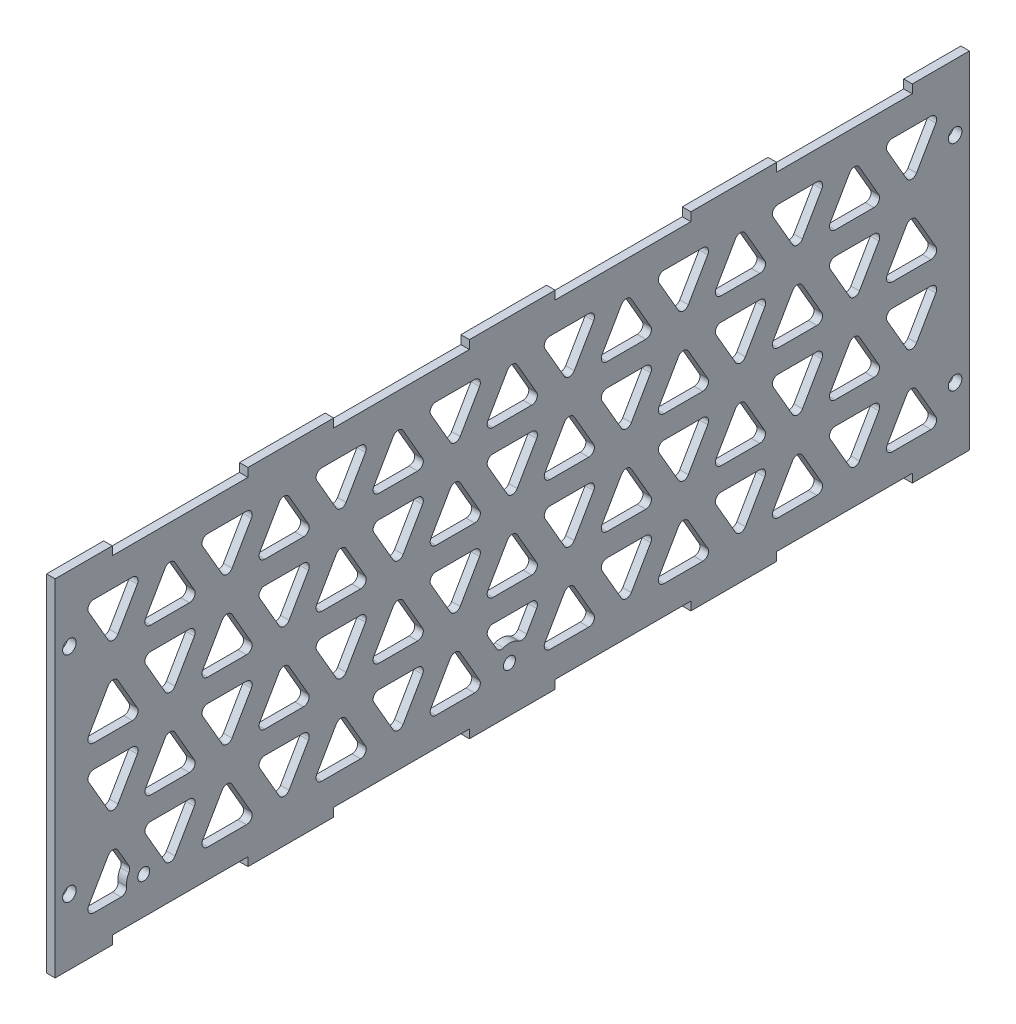
SolidWorks part; units mm, degrees
ref_plane "Front Plane" through (0, 0, 0) normal (0, 0, 1) x (1, 0, 0)
ref_plane "Top Plane" through (0, 0, 0) normal (0, 1, 0) x (1, 0, 0)
ref_plane "Right Plane" through (0, 0, 0) normal (1, 0, 0) x (0, 0, -1)
sketch "Sketch1" plane through (0, 0, 0) normal (1, 0, 0) x (0, 0, -1)
  line L1 (-160, -57.5) -> (160, -57.5)
  line L2 (-160, -57.5) -> (-160, 57.5)
  line L3 (-160, 57.5) -> (160, 57.5)
  line L4 (160, -57.5) -> (160, 57.5)
  line L5 (-160, -57.5) -> (160, 57.5) construction
  line L6 (-160, 57.5) -> (160, -57.5) construction
  point P0 (0, 0)
  dimension "D1" = 320
  dimension "D2" = 115
extrude "Boss-Extrude1" add sketch "Sketch1" along normal mid plane 3
sketch "Sketch2" plane through (1.5, 0, 0) normal (1, 0, 0) x (0, 0, -1)
  line L0 (160, 57.5) -> (-160, 57.5) construction
  line L1 (-160, 57.5) -> (-140, 57.5)
  line L2 (-160, 57.5) -> (-160, 60.5)
  line L3 (-160, 60.5) -> (-140, 60.5)
  line L4 (-140, 57.5) -> (-140, 60.5)
  line L5 (-92.5, 57.5) -> (-62.5, 57.5)
  line L6 (-92.5, 57.5) -> (-92.5, 60.5)
  line L7 (-92.5, 60.5) -> (-62.5, 60.5)
  line L8 (-62.5, 57.5) -> (-62.5, 60.5)
  line L9 (-15, 57.5) -> (-15, 60.5)
  line L10 (-15, 57.5) -> (15, 57.5)
  line L11 (15, 57.5) -> (15, 60.5)
  line L12 (-15, 60.5) -> (15, 60.5)
  line L13 (62.5, 57.5) -> (62.5, 60.5)
  line L14 (62.5, 57.5) -> (92.5, 57.5)
  line L15 (92.5, 57.5) -> (92.5, 60.5)
  line L16 (62.5, 60.5) -> (92.5, 60.5)
  line L17 (0, 57.5) -> (0, -57.5) construction
  line L18 (-160, -57.5) -> (160, -57.5) construction
  line L19 (140, 57.5) -> (140, 60.5)
  line L20 (160, 60.5) -> (140, 60.5)
  line L21 (160, 57.5) -> (160, 60.5)
  line L22 (160, 57.5) -> (140, 57.5)
  point P11 (-140, 59)
  dimension "D1" = 3
  dimension "D2" = 20
  dimension "D3" = 30
  dimension "D4" = 47.5
  dimension "D6" = 47.5
  dimension "D5" = 3
extrude "Boss-Extrude2" add sketch "Sketch2" along direction (-1, 0, 0) on the side against the normal up to surface (3 mm away) up to face at (-1.5, 0, 0)
mirror "Mirror1" about plane through (0, 0, 0) normal (0, 1, 0) of "Boss-Extrude2"
sketch "Sketch3" plane through (1.5, 0, 0) normal (1, 0, 0) x (0, 0, -1)
  line L1 (-148, -44.5) -> (-66, -44.5)
  line L2 (-148, -44.5) -> (-148, 12.5)
  line L3 (-148, 12.5) -> (-66, 12.5)
  line L4 (-66, -44.5) -> (-66, 12.5)
  line L5 (92.5, -57.5) -> (140, -57.5) construction
  line L7 (-160, 60.5) -> (-160, -60.5) construction
  dimension "D1" = 82
  dimension "D2" = 12
  dimension "D3" = 13
  dimension "D4" = 70
sketch "Sketch4" plane through (-1.5, 0, 0) normal (-1, 0, 0) x (0, 0, 1)
  line L0 (1.65, 0) -> (-1.65, 0) construction
  line L1 (0, -1.65) -> (0, 1.65) construction
  circle A0 centre (155, -37.5) radius 2.375
  circle A2 centre (155, -37.5) radius 2.5 construction
  circle A3 centre (155, 37.5) radius 2.375
  circle A4 centre (-155, -37.5) radius 2.375
  circle A5 centre (-155, 37.5) radius 2.375
  dimension "D1" = 4.75
extrude "Cut-Extrude3" cut sketch "Sketch4" against normal up to next
sketch "Sketch5" plane through (1.5, 0, 0) normal (1, 0, 0) x (0, 0, -1)
  line L0 (129.5041, 47.5) -> (150, 47.5)
  line L1 (150, 47.5) -> (139.752, 29.75)
  line L2 (139.752, 29.75) -> (129.5041, 47.5)
  line L3 (119.7875, 47.5) -> (130.0354, 29.75)
  line L4 (130.0354, 29.75) -> (109.5395, 29.75)
  line L5 (109.5395, 29.75) -> (119.7875, 47.5)
  line L24 (140, 57.5) -> (92.5, 57.5) construction
  line L25 (160, -60.5) -> (160, 60.5) construction
  line L26 (109.5395, 25.75) -> (150, 25.75) construction
  line L27 (160, 0) -> (-160, 0) construction
  line L28 (-160, 60.5) -> (-160, -60.5) construction
  line L29 (109.5395, 21.75) -> (119.7875, 4)
  line L30 (130.0354, 21.75) -> (109.5395, 21.75)
  line L31 (119.7875, 4) -> (130.0354, 21.75)
  line L32 (139.752, 21.75) -> (129.5041, 4)
  line L33 (150, 4) -> (139.752, 21.75)
  line L34 (129.5041, 4) -> (150, 4)
  line L35 (129.5041, 47.5) -> (150, 47.5)
  line L36 (150, 47.5) -> (139.752, 29.75)
  line L37 (139.752, 29.75) -> (129.5041, 47.5)
  line L38 (119.7875, 47.5) -> (130.0354, 29.75)
  line L39 (130.0354, 29.75) -> (109.5395, 29.75)
  line L40 (109.5395, 29.75) -> (119.7875, 47.5)
  line L41 (109.5395, 21.75) -> (119.7875, 4)
  line L42 (130.0354, 21.75) -> (109.5395, 21.75)
  line L43 (119.7875, 4) -> (130.0354, 21.75)
  line L44 (139.752, 21.75) -> (129.5041, 4)
  line L45 (150, 4) -> (139.752, 21.75)
  line L46 (129.5041, 4) -> (150, 4)
  line L47 (109.5395, -25.75) -> (150, -25.75) construction
  line L48 (129.5041, -4) -> (150, -4)
  line L49 (150, -4) -> (139.752, -21.75)
  line L50 (139.752, -21.75) -> (129.5041, -4)
  line L51 (119.7875, -4) -> (130.0354, -21.75)
  line L52 (130.0354, -21.75) -> (109.5395, -21.75)
  line L53 (109.5395, -21.75) -> (119.7875, -4)
  line L54 (109.5395, -29.75) -> (119.7875, -47.5)
  line L55 (130.0354, -29.75) -> (109.5395, -29.75)
  line L56 (119.7875, -47.5) -> (130.0354, -29.75)
  line L57 (139.752, -29.75) -> (129.5041, -47.5)
  line L58 (150, -47.5) -> (139.752, -29.75)
  line L59 (129.5041, -47.5) -> (150, -47.5)
  line L60 (129.5041, -4) -> (150, -4)
  line L61 (150, -4) -> (139.752, -21.75)
  line L62 (139.752, -21.75) -> (129.5041, -4)
  line L63 (119.7875, -4) -> (130.0354, -21.75)
  line L64 (130.0354, -21.75) -> (109.5395, -21.75)
  line L65 (109.5395, -21.75) -> (119.7875, -4)
  line L66 (109.5395, -29.75) -> (119.7875, -47.5)
  line L67 (130.0354, -29.75) -> (109.5395, -29.75)
  line L68 (119.7875, -47.5) -> (130.0354, -29.75)
  line L69 (139.752, -29.75) -> (129.5041, -47.5)
  line L70 (150, -47.5) -> (139.752, -29.75)
  line L71 (129.5041, -47.5) -> (150, -47.5)
  line L72 (89.5749, 47.5) -> (110.0708, 47.5)
  line L73 (110.0708, 47.5) -> (99.8229, 29.75)
  line L74 (99.8229, 29.75) -> (89.5749, 47.5)
  line L75 (79.8583, 47.5) -> (90.1063, 29.75)
  line L76 (90.1063, 29.75) -> (69.6103, 29.75)
  line L77 (69.6103, 29.75) -> (79.8583, 47.5)
  line L78 (69.6103, 21.75) -> (79.8583, 4)
  line L79 (90.1063, 21.75) -> (69.6103, 21.75)
  line L80 (79.8583, 4) -> (90.1063, 21.75)
  line L81 (99.8229, 21.75) -> (89.5749, 4)
  line L82 (110.0708, 4) -> (99.8229, 21.75)
  line L83 (89.5749, 4) -> (110.0708, 4)
  line L84 (89.5749, 47.5) -> (110.0708, 47.5)
  line L85 (110.0708, 47.5) -> (99.8229, 29.75)
  line L86 (99.8229, 29.75) -> (89.5749, 47.5)
  line L87 (79.8583, 47.5) -> (90.1063, 29.75)
  line L88 (90.1063, 29.75) -> (69.6103, 29.75)
  line L89 (69.6103, 29.75) -> (79.8583, 47.5)
  line L90 (69.6103, 21.75) -> (79.8583, 4)
  line L91 (90.1063, 21.75) -> (69.6103, 21.75)
  line L92 (79.8583, 4) -> (90.1063, 21.75)
  line L93 (99.8229, 21.75) -> (89.5749, 4)
  line L94 (110.0708, 4) -> (99.8229, 21.75)
  line L95 (89.5749, 4) -> (110.0708, 4)
  line L96 (89.5749, -4) -> (110.0708, -4)
  line L97 (110.0708, -4) -> (99.8229, -21.75)
  line L98 (99.8229, -21.75) -> (89.5749, -4)
  line L99 (79.8583, -4) -> (90.1063, -21.75)
  line L100 (90.1063, -21.75) -> (69.6103, -21.75)
  line L101 (69.6103, -21.75) -> (79.8583, -4)
  line L102 (69.6103, -29.75) -> (79.8583, -47.5)
  line L103 (90.1063, -29.75) -> (69.6103, -29.75)
  line L104 (79.8583, -47.5) -> (90.1063, -29.75)
  line L105 (99.8229, -29.75) -> (89.5749, -47.5)
  line L106 (110.0708, -47.5) -> (99.8229, -29.75)
  line L107 (89.5749, -47.5) -> (110.0708, -47.5)
  line L108 (89.5749, -4) -> (110.0708, -4)
  line L109 (110.0708, -4) -> (99.8229, -21.75)
  line L110 (99.8229, -21.75) -> (89.5749, -4)
  line L111 (79.8583, -4) -> (90.1063, -21.75)
  line L112 (90.1063, -21.75) -> (69.6103, -21.75)
  line L113 (69.6103, -21.75) -> (79.8583, -4)
  line L114 (69.6103, -29.75) -> (79.8583, -47.5)
  line L115 (90.1063, -29.75) -> (69.6103, -29.75)
  line L116 (79.8583, -47.5) -> (90.1063, -29.75)
  line L117 (99.8229, -29.75) -> (89.5749, -47.5)
  line L118 (110.0708, -47.5) -> (99.8229, -29.75)
  line L119 (89.5749, -47.5) -> (110.0708, -47.5)
  line L120 (110.0708, 47.5) -> (119.7875, 47.5) construction
  line L121 (129.5041, 47.5) -> (119.7875, 47.5) construction
  line L122 (49.6458, 47.5) -> (70.1417, 47.5)
  line L123 (70.1417, 47.5) -> (59.8937, 29.75)
  line L124 (59.8937, 29.75) -> (49.6458, 47.5)
  line L125 (39.9292, 47.5) -> (50.1771, 29.75)
  line L126 (50.1771, 29.75) -> (29.6812, 29.75)
  line L127 (29.6812, 29.75) -> (39.9292, 47.5)
  line L128 (29.6812, 21.75) -> (39.9292, 4)
  line L129 (50.1771, 21.75) -> (29.6812, 21.75)
  line L130 (39.9292, 4) -> (50.1771, 21.75)
  line L131 (59.8937, 21.75) -> (49.6458, 4)
  line L132 (70.1417, 4) -> (59.8937, 21.75)
  line L133 (49.6458, 4) -> (70.1417, 4)
  line L134 (49.6458, 47.5) -> (70.1417, 47.5)
  line L135 (70.1417, 47.5) -> (59.8937, 29.75)
  line L136 (59.8937, 29.75) -> (49.6458, 47.5)
  line L137 (39.9292, 47.5) -> (50.1771, 29.75)
  line L138 (50.1771, 29.75) -> (29.6812, 29.75)
  line L139 (29.6812, 29.75) -> (39.9292, 47.5)
  line L140 (29.6812, 21.75) -> (39.9292, 4)
  line L141 (50.1771, 21.75) -> (29.6812, 21.75)
  line L142 (39.9292, 4) -> (50.1771, 21.75)
  line L143 (59.8937, 21.75) -> (49.6458, 4)
  line L144 (70.1417, 4) -> (59.8937, 21.75)
  line L145 (49.6458, 4) -> (70.1417, 4)
  line L146 (49.6458, -4) -> (70.1417, -4)
  line L147 (70.1417, -4) -> (59.8937, -21.75)
  line L148 (59.8937, -21.75) -> (49.6458, -4)
  line L149 (39.9292, -4) -> (50.1771, -21.75)
  line L150 (50.1771, -21.75) -> (29.6812, -21.75)
  line L151 (29.6812, -21.75) -> (39.9292, -4)
  line L152 (29.6812, -29.75) -> (39.9292, -47.5)
  line L153 (50.1771, -29.75) -> (29.6812, -29.75)
  line L154 (39.9292, -47.5) -> (50.1771, -29.75)
  line L155 (59.8937, -29.75) -> (49.6458, -47.5)
  line L156 (70.1417, -47.5) -> (59.8937, -29.75)
  line L157 (49.6458, -47.5) -> (70.1417, -47.5)
  line L158 (49.6458, -4) -> (70.1417, -4)
  line L159 (70.1417, -4) -> (59.8937, -21.75)
  line L160 (59.8937, -21.75) -> (49.6458, -4)
  line L161 (39.9292, -4) -> (50.1771, -21.75)
  line L162 (50.1771, -21.75) -> (29.6812, -21.75)
  line L163 (29.6812, -21.75) -> (39.9292, -4)
  line L164 (29.6812, -29.75) -> (39.9292, -47.5)
  line L165 (50.1771, -29.75) -> (29.6812, -29.75)
  line L166 (39.9292, -47.5) -> (50.1771, -29.75)
  line L167 (59.8937, -29.75) -> (49.6458, -47.5)
  line L168 (70.1417, -47.5) -> (59.8937, -29.75)
  line L169 (49.6458, -47.5) -> (70.1417, -47.5)
  line L170 (-90.1063, 21.75) -> (-79.8583, 4)
  line L171 (-69.6103, 21.75) -> (-90.1063, 21.75)
  line L172 (9.7166, 47.5) -> (30.2125, 47.5)
  line L173 (30.2125, 47.5) -> (19.9646, 29.75)
  line L174 (19.9646, 29.75) -> (9.7166, 47.5)
  line L175 (0, 47.5) -> (10.248, 29.75)
  line L176 (10.248, 29.75) -> (-10.248, 29.75)
  line L177 (-10.248, 29.75) -> (0, 47.5)
  line L178 (-10.248, 21.75) -> (0, 4)
  line L179 (10.248, 21.75) -> (-10.248, 21.75)
  line L180 (0, 4) -> (10.248, 21.75)
  line L181 (19.9646, 21.75) -> (9.7166, 4)
  line L182 (30.2125, 4) -> (19.9646, 21.75)
  line L183 (9.7166, 4) -> (30.2125, 4)
  line L184 (9.7166, 47.5) -> (30.2125, 47.5)
  line L185 (30.2125, 47.5) -> (19.9646, 29.75)
  line L186 (19.9646, 29.75) -> (9.7166, 47.5)
  line L187 (0, 47.5) -> (10.248, 29.75)
  line L188 (10.248, 29.75) -> (-10.248, 29.75)
  line L189 (-10.248, 29.75) -> (0, 47.5)
  line L190 (-10.248, 21.75) -> (0, 4)
  line L191 (10.248, 21.75) -> (-10.248, 21.75)
  line L192 (0, 4) -> (10.248, 21.75)
  line L193 (19.9646, 21.75) -> (9.7166, 4)
  line L194 (30.2125, 4) -> (19.9646, 21.75)
  line L195 (9.7166, 4) -> (30.2125, 4)
  line L196 (9.7166, -4) -> (30.2125, -4)
  line L197 (30.2125, -4) -> (19.9646, -21.75)
  line L198 (19.9646, -21.75) -> (9.7166, -4)
  line L199 (0, -4) -> (10.248, -21.75)
  line L200 (10.248, -21.75) -> (-10.248, -21.75)
  line L201 (-10.248, -21.75) -> (0, -4)
  line L202 (-10.248, -29.75) -> (0, -47.5)
  line L203 (10.248, -29.75) -> (-10.248, -29.75)
  line L204 (0, -47.5) -> (10.248, -29.75)
  line L205 (19.9646, -29.75) -> (9.7166, -47.5)
  line L206 (30.2125, -47.5) -> (19.9646, -29.75)
  line L207 (9.7166, -47.5) -> (30.2125, -47.5)
  line L208 (9.7166, -4) -> (30.2125, -4)
  line L209 (30.2125, -4) -> (19.9646, -21.75)
  line L210 (19.9646, -21.75) -> (9.7166, -4)
  line L211 (0, -4) -> (10.248, -21.75)
  line L212 (10.248, -21.75) -> (-10.248, -21.75)
  line L213 (-10.248, -21.75) -> (0, -4)
  line L214 (-10.248, -29.75) -> (0, -47.5)
  line L215 (10.248, -29.75) -> (-10.248, -29.75)
  line L216 (0, -47.5) -> (10.248, -29.75)
  line L217 (19.9646, -29.75) -> (9.7166, -47.5)
  line L218 (30.2125, -47.5) -> (19.9646, -29.75)
  line L219 (9.7166, -47.5) -> (30.2125, -47.5)
  line L220 (-79.8583, 4) -> (-69.6103, 21.75)
  line L221 (-59.8937, 21.75) -> (-70.1417, 4)
  line L222 (-30.2125, 47.5) -> (-9.7166, 47.5)
  line L223 (-9.7166, 47.5) -> (-19.9646, 29.75)
  line L224 (-19.9646, 29.75) -> (-30.2125, 47.5)
  line L225 (-39.9292, 47.5) -> (-29.6812, 29.75)
  line L226 (-29.6812, 29.75) -> (-50.1771, 29.75)
  line L227 (-50.1771, 29.75) -> (-39.9292, 47.5)
  line L228 (-50.1771, 21.75) -> (-39.9292, 4)
  line L229 (-29.6812, 21.75) -> (-50.1771, 21.75)
  line L230 (-39.9292, 4) -> (-29.6812, 21.75)
  line L231 (-19.9646, 21.75) -> (-30.2125, 4)
  line L232 (-9.7166, 4) -> (-19.9646, 21.75)
  line L233 (-30.2125, 4) -> (-9.7166, 4)
  line L234 (-30.2125, 47.5) -> (-9.7166, 47.5)
  line L235 (-9.7166, 47.5) -> (-19.9646, 29.75)
  line L236 (-19.9646, 29.75) -> (-30.2125, 47.5)
  line L237 (-39.9292, 47.5) -> (-29.6812, 29.75)
  line L238 (-29.6812, 29.75) -> (-50.1771, 29.75)
  line L239 (-50.1771, 29.75) -> (-39.9292, 47.5)
  line L240 (-50.1771, 21.75) -> (-39.9292, 4)
  line L241 (-29.6812, 21.75) -> (-50.1771, 21.75)
  line L242 (-39.9292, 4) -> (-29.6812, 21.75)
  line L243 (-19.9646, 21.75) -> (-30.2125, 4)
  line L244 (-9.7166, 4) -> (-19.9646, 21.75)
  line L245 (-30.2125, 4) -> (-9.7166, 4)
  line L246 (-30.2125, -4) -> (-9.7166, -4)
  line L247 (-9.7166, -4) -> (-19.9646, -21.75)
  line L248 (-19.9646, -21.75) -> (-30.2125, -4)
  line L249 (-39.9292, -4) -> (-29.6812, -21.75)
  line L250 (-29.6812, -21.75) -> (-50.1771, -21.75)
  line L251 (-50.1771, -21.75) -> (-39.9292, -4)
  line L252 (-50.1771, -29.75) -> (-39.9292, -47.5)
  line L253 (-29.6812, -29.75) -> (-50.1771, -29.75)
  line L254 (-39.9292, -47.5) -> (-29.6812, -29.75)
  line L255 (-19.9646, -29.75) -> (-30.2125, -47.5)
  line L256 (-9.7166, -47.5) -> (-19.9646, -29.75)
  line L257 (-30.2125, -47.5) -> (-9.7166, -47.5)
  line L258 (-30.2125, -4) -> (-9.7166, -4)
  line L259 (-9.7166, -4) -> (-19.9646, -21.75)
  line L260 (-19.9646, -21.75) -> (-30.2125, -4)
  line L261 (-39.9292, -4) -> (-29.6812, -21.75)
  line L262 (-29.6812, -21.75) -> (-50.1771, -21.75)
  line L263 (-50.1771, -21.75) -> (-39.9292, -4)
  line L264 (-50.1771, -29.75) -> (-39.9292, -47.5)
  line L265 (-29.6812, -29.75) -> (-50.1771, -29.75)
  line L266 (-39.9292, -47.5) -> (-29.6812, -29.75)
  line L267 (-19.9646, -29.75) -> (-30.2125, -47.5)
  line L268 (-9.7166, -47.5) -> (-19.9646, -29.75)
  line L269 (-30.2125, -47.5) -> (-9.7166, -47.5)
  line L270 (-49.6458, 4) -> (-59.8937, 21.75)
  line L271 (-70.1417, 4) -> (-49.6458, 4)
  line L272 (-70.1417, 47.5) -> (-49.6458, 47.5)
  line L273 (-49.6458, 47.5) -> (-59.8937, 29.75)
  line L274 (-59.8937, 29.75) -> (-70.1417, 47.5)
  line L275 (-79.8583, 47.5) -> (-69.6103, 29.75)
  line L276 (-69.6103, 29.75) -> (-90.1063, 29.75)
  line L277 (-90.1063, 29.75) -> (-79.8583, 47.5)
  line L278 (-90.1063, 21.75) -> (-79.8583, 4)
  line L279 (-69.6103, 21.75) -> (-90.1063, 21.75)
  line L280 (-79.8583, 4) -> (-69.6103, 21.75)
  line L281 (-59.8937, 21.75) -> (-70.1417, 4)
  line L282 (-49.6458, 4) -> (-59.8937, 21.75)
  line L283 (-70.1417, 4) -> (-49.6458, 4)
  line L284 (-70.1417, 47.5) -> (-49.6458, 47.5)
  line L285 (-49.6458, 47.5) -> (-59.8937, 29.75)
  line L286 (-59.8937, 29.75) -> (-70.1417, 47.5)
  line L287 (-79.8583, 47.5) -> (-69.6103, 29.75)
  line L288 (-69.6103, 29.75) -> (-90.1063, 29.75)
  line L289 (-90.1063, 29.75) -> (-79.8583, 47.5)
  line L296 (-70.1417, -4) -> (-49.6458, -4)
  line L297 (-49.6458, -4) -> (-59.8937, -21.75)
  line L298 (-59.8937, -21.75) -> (-70.1417, -4)
  line L299 (-79.8583, -4) -> (-69.6103, -21.75)
  line L300 (-69.6103, -21.75) -> (-90.1063, -21.75)
  line L301 (-90.1063, -21.75) -> (-79.8583, -4)
  line L302 (-90.1063, -29.75) -> (-79.8583, -47.5)
  line L303 (-69.6103, -29.75) -> (-90.1063, -29.75)
  line L304 (-79.8583, -47.5) -> (-69.6103, -29.75)
  line L305 (-59.8937, -29.75) -> (-70.1417, -47.5)
  line L306 (-49.6458, -47.5) -> (-59.8937, -29.75)
  line L307 (-70.1417, -47.5) -> (-49.6458, -47.5)
  line L320 (-70.1417, -4) -> (-49.6458, -4)
  line L321 (-49.6458, -4) -> (-59.8937, -21.75)
  line L322 (-110.0708, 47.5) -> (-89.5749, 47.5)
  line L323 (-89.5749, 47.5) -> (-99.8229, 29.75)
  line L324 (-99.8229, 29.75) -> (-110.0708, 47.5)
  line L325 (-119.7875, 47.5) -> (-109.5395, 29.75)
  line L326 (-109.5395, 29.75) -> (-130.0354, 29.75)
  line L327 (-130.0354, 29.75) -> (-119.7875, 47.5)
  line L328 (-59.8937, -21.75) -> (-70.1417, -4)
  line L329 (-79.8583, -4) -> (-69.6103, -21.75)
  line L330 (-69.6103, -21.75) -> (-90.1063, -21.75)
  line L331 (-90.1063, -21.75) -> (-79.8583, -4)
  line L332 (-90.1063, -29.75) -> (-79.8583, -47.5)
  line L333 (-69.6103, -29.75) -> (-90.1063, -29.75)
  line L334 (-110.0708, 47.5) -> (-89.5749, 47.5)
  line L335 (-89.5749, 47.5) -> (-99.8229, 29.75)
  line L336 (-99.8229, 29.75) -> (-110.0708, 47.5)
  line L337 (-119.7875, 47.5) -> (-109.5395, 29.75)
  line L338 (-109.5395, 29.75) -> (-130.0354, 29.75)
  line L339 (-130.0354, 29.75) -> (-119.7875, 47.5)
  line L346 (-79.8583, -47.5) -> (-69.6103, -29.75)
  line L347 (-59.8937, -29.75) -> (-70.1417, -47.5)
  line L348 (-49.6458, -47.5) -> (-59.8937, -29.75)
  line L349 (-70.1417, -47.5) -> (-49.6458, -47.5)
  line L350 (-130.0354, 21.75) -> (-119.7875, 4)
  line L351 (-109.5395, 21.75) -> (-130.0354, 21.75)
  line L352 (-119.7875, 4) -> (-109.5395, 21.75)
  line L353 (-99.8229, 21.75) -> (-110.0708, 4)
  line L354 (-89.5749, 4) -> (-99.8229, 21.75)
  line L355 (-110.0708, 4) -> (-89.5749, 4)
  line L356 (-130.0354, 21.75) -> (-119.7875, 4)
  line L357 (-109.5395, 21.75) -> (-130.0354, 21.75)
  line L370 (-119.7875, 4) -> (-109.5395, 21.75)
  line L371 (-99.8229, 21.75) -> (-110.0708, 4)
  line L372 (-150, 47.5) -> (-129.5041, 47.5)
  line L373 (-129.5041, 47.5) -> (-139.752, 29.75)
  line L374 (-139.752, 29.75) -> (-150, 47.5)
  line L375 (-89.5749, 4) -> (-99.8229, 21.75)
  line L376 (-110.0708, 4) -> (-89.5749, 4)
  line L377 (-110.0708, -4) -> (-89.5749, -4)
  line L378 (-89.5749, -4) -> (-99.8229, -21.75)
  line L379 (-99.8229, -21.75) -> (-110.0708, -4)
  line L380 (-119.7875, -4) -> (-109.5395, -21.75)
  line L381 (-109.5395, -21.75) -> (-130.0354, -21.75)
  line L382 (-130.0354, -21.75) -> (-119.7875, -4)
  line L383 (-130.0354, -29.75) -> (-119.7875, -47.5)
  line L384 (-150, 47.5) -> (-129.5041, 47.5)
  line L385 (-129.5041, 47.5) -> (-139.752, 29.75)
  line L386 (-139.752, 29.75) -> (-150, 47.5)
  line L396 (-109.5395, -29.75) -> (-130.0354, -29.75)
  line L397 (-119.7875, -47.5) -> (-109.5395, -29.75)
  line L398 (-99.8229, -29.75) -> (-110.0708, -47.5)
  line L399 (-89.5749, -47.5) -> (-99.8229, -29.75)
  line L400 (-110.0708, -47.5) -> (-89.5749, -47.5)
  line L401 (-110.0708, -4) -> (-89.5749, -4)
  line L402 (-89.5749, -4) -> (-99.8229, -21.75)
  line L403 (-99.8229, -21.75) -> (-110.0708, -4)
  line L404 (-119.7875, -4) -> (-109.5395, -21.75)
  line L405 (-109.5395, -21.75) -> (-130.0354, -21.75)
  line L406 (-130.0354, -21.75) -> (-119.7875, -4)
  line L407 (-130.0354, -29.75) -> (-119.7875, -47.5)
  line L420 (-109.5395, -29.75) -> (-130.0354, -29.75)
  line L421 (-119.7875, -47.5) -> (-109.5395, -29.75)
  line L422 (150, 47.5) -> (160, 47.5) construction
  line L423 (-150, 47.5) -> (-160, 47.5) construction
  line L424 (-99.8229, -29.75) -> (-110.0708, -47.5)
  line L425 (-159.7166, 47.5) -> (-149.4686, 29.75) [skipped]
  line L426 (-149.4686, 29.75) -> (-169.9646, 29.75) [skipped]
  line L427 (-169.9646, 29.75) -> (-159.7166, 47.5) [skipped]
  line L428 (-169.9646, 21.75) -> (-159.7166, 4) [skipped]
  line L429 (-149.4686, 21.75) -> (-169.9646, 21.75) [skipped]
  line L430 (-159.7166, 4) -> (-149.4686, 21.75) [skipped]
  line L431 (-159.7166, 47.5) -> (-149.4686, 29.75) [skipped]
  line L432 (-149.4686, 29.75) -> (-169.9646, 29.75) [skipped]
  line L433 (-169.9646, 29.75) -> (-159.7166, 47.5) [skipped]
  line L434 (-169.9646, 21.75) -> (-159.7166, 4) [skipped]
  line L435 (-149.4686, 21.75) -> (-169.9646, 21.75) [skipped]
  line L436 (-159.7166, 4) -> (-149.4686, 21.75) [skipped]
  line L437 (-159.7166, -4) -> (-149.4686, -21.75) [skipped]
  line L438 (-149.4686, -21.75) -> (-169.9646, -21.75) [skipped]
  line L439 (-169.9646, -21.75) -> (-159.7166, -4) [skipped]
  line L440 (-169.9646, -29.75) -> (-159.7166, -47.5) [skipped]
  line L441 (-149.4686, -29.75) -> (-169.9646, -29.75) [skipped]
  line L442 (-159.7166, -47.5) -> (-149.4686, -29.75) [skipped]
  line L443 (-159.7166, -4) -> (-149.4686, -21.75) [skipped]
  line L444 (-149.4686, -21.75) -> (-169.9646, -21.75) [skipped]
  line L445 (-169.9646, -21.75) -> (-159.7166, -4) [skipped]
  line L446 (-169.9646, -29.75) -> (-159.7166, -47.5) [skipped]
  line L447 (-149.4686, -29.75) -> (-169.9646, -29.75) [skipped]
  line L448 (-159.7166, -47.5) -> (-149.4686, -29.75) [skipped]
  line L449 (-169.9646, 25.75) -> (-129.5041, 25.75) construction
  line L450 (-130.0354, 25.75) -> (-89.5749, 25.75) construction
  line L451 (-90.1063, 25.75) -> (-49.6458, 25.75) construction
  line L452 (-50.1771, 25.75) -> (-9.7166, 25.75) construction
  line L453 (-10.248, 25.75) -> (30.2125, 25.75) construction
  line L454 (29.6812, 25.75) -> (70.1417, 25.75) construction
  line L455 (69.6103, 25.75) -> (110.0708, 25.75) construction
  line L456 (69.6103, -25.75) -> (110.0708, -25.75) construction
  line L457 (29.6812, -25.75) -> (70.1417, -25.75) construction
  line L458 (-10.248, -25.75) -> (30.2125, -25.75) construction
  line L459 (-50.1771, -25.75) -> (-9.7166, -25.75) construction
  line L460 (-90.1063, -25.75) -> (-49.6458, -25.75) construction
  line L461 (-130.0354, -25.75) -> (-89.5749, -25.75) construction
  line L462 (-169.9646, -25.75) -> (-129.5041, -25.75) construction
  line L463 (-90.1063, 21.75) -> (-79.8583, 4) [skipped]
  line L464 (-69.6103, 21.75) -> (-90.1063, 21.75) [skipped]
  line L465 (-79.8583, 4) -> (-69.6103, 21.75) [skipped]
  line L466 (-59.8937, 21.75) -> (-70.1417, 4) [skipped]
  line L467 (-49.6458, 4) -> (-59.8937, 21.75) [skipped]
  line L468 (-70.1417, 4) -> (-49.6458, 4) [skipped]
  line L469 (-90.1063, 21.75) -> (-79.8583, 4) [skipped]
  line L470 (-69.6103, 21.75) -> (-90.1063, 21.75) [skipped]
  line L471 (-79.8583, 4) -> (-69.6103, 21.75) [skipped]
  line L472 (-59.8937, 21.75) -> (-70.1417, 4) [skipped]
  line L473 (-49.6458, 4) -> (-59.8937, 21.75) [skipped]
  line L474 (-70.1417, 4) -> (-49.6458, 4) [skipped]
  line L475 (-70.1417, -4) -> (-49.6458, -4) [skipped]
  line L476 (-49.6458, -4) -> (-59.8937, -21.75) [skipped]
  line L477 (-59.8937, -21.75) -> (-70.1417, -4) [skipped]
  line L478 (-79.8583, -4) -> (-69.6103, -21.75) [skipped]
  line L479 (-69.6103, -21.75) -> (-90.1063, -21.75) [skipped]
  line L480 (-90.1063, -21.75) -> (-79.8583, -4) [skipped]
  line L481 (-90.1063, -29.75) -> (-79.8583, -47.5) [skipped]
  line L482 (-69.6103, -29.75) -> (-90.1063, -29.75) [skipped]
  line L483 (-79.8583, -47.5) -> (-69.6103, -29.75) [skipped]
  line L484 (-59.8937, -29.75) -> (-70.1417, -47.5) [skipped]
  line L485 (-49.6458, -47.5) -> (-59.8937, -29.75) [skipped]
  line L486 (-70.1417, -47.5) -> (-49.6458, -47.5) [skipped]
  line L487 (-70.1417, -4) -> (-49.6458, -4) [skipped]
  line L488 (-49.6458, -4) -> (-59.8937, -21.75) [skipped]
  line L489 (-59.8937, -21.75) -> (-70.1417, -4) [skipped]
  line L490 (-79.8583, -4) -> (-69.6103, -21.75) [skipped]
  line L491 (-69.6103, -21.75) -> (-90.1063, -21.75) [skipped]
  line L492 (-90.1063, -21.75) -> (-79.8583, -4) [skipped]
  line L493 (-90.1063, -29.75) -> (-79.8583, -47.5) [skipped]
  line L494 (-69.6103, -29.75) -> (-90.1063, -29.75) [skipped]
  line L495 (-79.8583, -47.5) -> (-69.6103, -29.75) [skipped]
  line L496 (-59.8937, -29.75) -> (-70.1417, -47.5) [skipped]
  line L497 (-49.6458, -47.5) -> (-59.8937, -29.75) [skipped]
  line L498 (-70.1417, -47.5) -> (-49.6458, -47.5) [skipped]
  line L499 (-130.0354, 21.75) -> (-119.7875, 4) [skipped]
  line L500 (-109.5395, 21.75) -> (-130.0354, 21.75) [skipped]
  line L501 (-119.7875, 4) -> (-109.5395, 21.75) [skipped]
  line L502 (-99.8229, 21.75) -> (-110.0708, 4) [skipped]
  line L503 (-89.5749, 4) -> (-99.8229, 21.75) [skipped]
  line L504 (-110.0708, 4) -> (-89.5749, 4) [skipped]
  line L505 (-130.0354, 21.75) -> (-119.7875, 4) [skipped]
  line L506 (-109.5395, 21.75) -> (-130.0354, 21.75) [skipped]
  line L507 (-119.7875, 4) -> (-109.5395, 21.75) [skipped]
  line L508 (-99.8229, 21.75) -> (-110.0708, 4) [skipped]
  line L509 (-89.5749, 4) -> (-99.8229, 21.75) [skipped]
  line L510 (-110.0708, 4) -> (-89.5749, 4) [skipped]
  line L511 (-110.0708, -4) -> (-89.5749, -4) [skipped]
  line L512 (-89.5749, -4) -> (-99.8229, -21.75) [skipped]
  line L513 (-99.8229, -21.75) -> (-110.0708, -4) [skipped]
  line L514 (-119.7875, -4) -> (-109.5395, -21.75) [skipped]
  line L515 (-109.5395, -21.75) -> (-130.0354, -21.75) [skipped]
  line L516 (-130.0354, -21.75) -> (-119.7875, -4) [skipped]
  line L517 (-130.0354, -29.75) -> (-119.7875, -47.5) [skipped]
  line L518 (-109.5395, -29.75) -> (-130.0354, -29.75) [skipped]
  line L519 (-119.7875, -47.5) -> (-109.5395, -29.75) [skipped]
  line L520 (-99.8229, -29.75) -> (-110.0708, -47.5) [skipped]
  line L521 (-89.5749, -47.5) -> (-99.8229, -29.75) [skipped]
  line L522 (-110.0708, -47.5) -> (-89.5749, -47.5) [skipped]
  line L523 (-110.0708, -4) -> (-89.5749, -4) [skipped]
  line L524 (-89.5749, -4) -> (-99.8229, -21.75) [skipped]
  line L525 (-99.8229, -21.75) -> (-110.0708, -4) [skipped]
  line L526 (-119.7875, -4) -> (-109.5395, -21.75) [skipped]
  line L527 (-109.5395, -21.75) -> (-130.0354, -21.75) [skipped]
  line L528 (-130.0354, -21.75) -> (-119.7875, -4) [skipped]
  line L529 (-130.0354, -29.75) -> (-119.7875, -47.5) [skipped]
  line L530 (-109.5395, -29.75) -> (-130.0354, -29.75) [skipped]
  line L531 (-119.7875, -47.5) -> (-109.5395, -29.75) [skipped]
  line L532 (-99.8229, -29.75) -> (-110.0708, -47.5) [skipped]
  line L533 (-89.5749, -47.5) -> (-99.8229, -29.75) [skipped]
  line L534 (-110.0708, -47.5) -> (-89.5749, -47.5) [skipped]
  line L535 (-139.752, 21.75) -> (-150, 4) [skipped]
  line L536 (-129.5041, 4) -> (-139.752, 21.75) [skipped]
  line L537 (-150, 4) -> (-129.5041, 4) [skipped]
  line L538 (-139.752, 21.75) -> (-150, 4) [skipped]
  line L539 (-129.5041, 4) -> (-139.752, 21.75) [skipped]
  line L540 (-150, 4) -> (-129.5041, 4) [skipped]
  line L541 (-150, -4) -> (-129.5041, -4) [skipped]
  line L542 (-129.5041, -4) -> (-139.752, -21.75) [skipped]
  line L543 (-139.752, -21.75) -> (-150, -4) [skipped]
  line L544 (-139.752, -29.75) -> (-150, -47.5) [skipped]
  line L545 (-129.5041, -47.5) -> (-139.752, -29.75) [skipped]
  line L546 (-150, -47.5) -> (-129.5041, -47.5) [skipped]
  line L547 (-150, -4) -> (-129.5041, -4) [skipped]
  line L548 (-129.5041, -4) -> (-139.752, -21.75) [skipped]
  line L549 (-139.752, -21.75) -> (-150, -4) [skipped]
  line L550 (-139.752, -29.75) -> (-150, -47.5) [skipped]
  line L551 (-129.5041, -47.5) -> (-139.752, -29.75) [skipped]
  line L552 (-150, -47.5) -> (-129.5041, -47.5) [skipped]
  line L553 (-89.5749, -47.5) -> (-99.8229, -29.75)
  line L554 (-110.0708, -47.5) -> (-89.5749, -47.5)
  line L558 (-139.752, 21.75) -> (-150, 4)
  line L559 (-129.5041, 4) -> (-139.752, 21.75)
  line L560 (-150, 4) -> (-129.5041, 4)
  line L564 (-139.752, 21.75) -> (-150, 4)
  line L565 (-129.5041, 4) -> (-139.752, 21.75)
  line L566 (-150, 4) -> (-129.5041, 4)
  line L567 (-150, -4) -> (-129.5041, -4)
  line L568 (-129.5041, -4) -> (-139.752, -21.75)
  line L569 (-139.752, -21.75) -> (-150, -4)
  line L576 (-139.752, -29.75) -> (-150, -47.5)
  line L577 (-129.5041, -47.5) -> (-139.752, -29.75)
  line L578 (-150, -47.5) -> (-129.5041, -47.5)
  line L579 (-150, -4) -> (-129.5041, -4)
  line L580 (-129.5041, -4) -> (-139.752, -21.75)
  line L581 (-139.752, -21.75) -> (-150, -4)
  line L588 (-139.752, -29.75) -> (-150, -47.5)
  line L589 (-129.5041, -47.5) -> (-139.752, -29.75)
  line L590 (-150, -47.5) -> (-129.5041, -47.5)
  line L591 (-169.9646, 21.75) -> (-159.7166, 4) [skipped]
  line L592 (-149.4686, 21.75) -> (-169.9646, 21.75) [skipped]
  line L593 (-159.7166, 4) -> (-149.4686, 21.75) [skipped]
  line L594 (-169.9646, 21.75) -> (-159.7166, 4) [skipped]
  line L595 (-149.4686, 21.75) -> (-169.9646, 21.75) [skipped]
  line L596 (-159.7166, 4) -> (-149.4686, 21.75) [skipped]
  line L597 (-159.7166, -4) -> (-149.4686, -21.75) [skipped]
  line L598 (-149.4686, -21.75) -> (-169.9646, -21.75) [skipped]
  line L599 (-169.9646, -21.75) -> (-159.7166, -4) [skipped]
  line L600 (-169.9646, -29.75) -> (-159.7166, -47.5) [skipped]
  line L601 (-149.4686, -29.75) -> (-169.9646, -29.75) [skipped]
  line L602 (-159.7166, -47.5) -> (-149.4686, -29.75) [skipped]
  line L603 (-159.7166, -4) -> (-149.4686, -21.75) [skipped]
  line L604 (-149.4686, -21.75) -> (-169.9646, -21.75) [skipped]
  line L605 (-169.9646, -21.75) -> (-159.7166, -4) [skipped]
  line L606 (-169.9646, -29.75) -> (-159.7166, -47.5) [skipped]
  line L607 (-149.4686, -29.75) -> (-169.9646, -29.75) [skipped]
  line L608 (-159.7166, -47.5) -> (-149.4686, -29.75) [skipped]
  point P22 (0, 0)
  dimension "D1" = 10
  dimension "D2" = 10
  dimension "D3" = 4
  dimension "D4" = 4
  dimension "D5" = 4
  dimension "D6" = 8
extrude "Cut-Extrude4" cut sketch "Sketch5" against normal up to next (3 mm away) contours L374 L373 L372 | L327 L326 L325 | L324 L323 L322 | L277 L276 L275 | L274 L273 L272 | L227 L226 L225 | L224 L223 L222 | L177 L176 L175 | L174 L173 L172 | L127 L126 L125 | L124 L123 L122 | L77 L76 L75 | L74 L73 L72 | L5 L4 L3 | L2 L1 L0 | L32 L34 L33 | L50 L49 L48 | L57 L59 L58 | L54 L56 L55 | L53 L52 L51 | L29 L31 L30 | L81 L83 L82 | L98 L97 L96 | L105 L107 L106 | L102 L104 L103 | L101 L100 L99 | L78 L80 L79 | L131 L133 L132 | L148 L147 L146 | L155 L157 L156 | L152 L154 L153 | L151 L150 L149 | L128 L130 L129 | L181 L183 L182 | L198 L197 L196 | L205 L207 L206 | L202 L204 L203 | L201 L200 L199 | L178 L180 L179 | L231 L233 L232 | L228 L230 L229 | L251 L250 L249 | L248 L247 L246 | L255 L257 L256 | L252 L254 L253 | L221 L271 L270 | L170 L220 L171 | L353 L355 L354 | L350 L352 L351 | L558 L560 L559 | L569 L568 L567 | L382 L381 L380 | L379 L378 L377 | L301 L300 L299 | L298 L297 L296 | L305 L307 L306 | L302 L304 L303 | L398 L400 L399 | L383 L397 L396 | L576 L578 L577 region at (1.5, 41.5833, -139.752) region at (1.5, 35.6667, -119.7875) region at (1.5, 15.8333, -119.7875) region at (1.5, 9.9167, -139.752) region at (1.5, -9.9167, -139.752) region at (1.5, -15.8333, -119.7875) region at (1.5, -35.6667, -119.7875) region at (1.5, -41.5833, -139.752) region at (1.5, 41.5833, -99.8229) region at (1.5, 35.6667, -79.8583) region at (1.5, 15.8333, -79.8583) region at (1.5, 9.9167, -99.8229) region at (1.5, -9.9167, -99.8229) region at (1.5, -15.8333, -79.8583) region at (1.5, -35.6667, -79.8583) region at (1.5, -41.5833, -99.8229) region at (1.5, 41.5833, -59.8937) region at (1.5, 35.6667, -39.9292) region at (1.5, 15.8333, -39.9292) region at (1.5, 9.9167, -59.8937) region at (1.5, -9.9167, -59.8937) region at (1.5, -15.8333, -39.9292) region at (1.5, -35.6667, -39.9292) region at (1.5, -41.5833, -59.8937) region at (1.5, 15.8333, 79.8583) region at (1.5, 41.5833, -19.9646) region at (1.5, 35.6667, 0) region at (1.5, 15.8333, 0) region at (1.5, 9.9167, -19.9646) region at (1.5, -9.9167, -19.9646) region at (1.5, -15.8333, 0) region at (1.5, -35.6667, 0) region at (1.5, -41.5833, -19.9646) region at (1.5, 9.9167, 59.8937) region at (1.5, 41.5833, 19.9646) region at (1.5, 35.6667, 39.9292) region at (1.5, 15.8333, 39.9292) region at (1.5, 9.9167, 19.9646) region at (1.5, -9.9167, 19.9646) region at (1.5, -15.8333, 39.9292) region at (1.5, -35.6667, 39.9292) region at (1.5, -41.5833, 19.9646) region at (1.5, 41.5833, 59.8937) region at (1.5, 35.6667, 79.8583) region at (1.5, -9.9167, 59.8937) region at (1.5, -15.8333, 79.8583) region at (1.5, -35.6667, 79.8583) region at (1.5, -41.5833, 59.8937) region at (1.5, 41.5833, 99.8229) region at (1.5, 35.6667, 119.7875) region at (1.5, 15.8333, 119.7875) region at (1.5, 9.9167, 99.8229) region at (1.5, 41.5833, 139.752) region at (1.5, -9.9167, 99.8229) region at (1.5, -15.8333, 119.7875) region at (1.5, -35.6667, 119.7875) region at (1.5, -41.5833, 99.8229) region at (1.5, 9.9167, 139.752) region at (1.5, -9.9167, 139.752) region at (1.5, -41.5833, 139.752)
sketch "Sketch6" plane through (-1.5, 0, 0) normal (-1, 0, 0) x (0, 0, 1)
  circle A0 centre (129, -44.5) radius 2.5 construction
  circle A1 centre (129, -44.5) radius 2.5 construction
  circle A2 centre (1, -44.5) radius 2.5 construction
  circle A3 centre (1, -44.5) radius 2.5 construction
  circle A4 centre (1, -44.5) radius 6
  circle A5 centre (129, -44.5) radius 6
  dimension "D1" = 12
extrude "Boss-Extrude4" add sketch "Sketch6" against normal through all
sketch "Sketch7" plane through (-1.5, 0, 0) normal (-1, 0, 0) x (0, 0, 1)
  circle A0 centre (1, -44.5) radius 2.1
  circle A1 centre (129, -44.5) radius 2.1
  dimension "D1" = 4.2
extrude "Cut-Extrude6" cut sketch "Sketch7" against normal through all
fillet "Fillet2" radius 2 182 edges at (0, 47.5, 129.5041) (0, 29.75, 139.752) (0, 47.5, 150) (0, -21.75, -10.248) (0, -21.75, 10.248) (0, -4, 0) (0, -4, -30.2125) (0, -21.75, -19.9646) (0, -4, -9.7166) (0, -21.75, 29.6812) (0, -21.75, 50.1771) (0, -4, 39.9292) (0, -4, 9.7166) (0, -21.75, 19.9646) (0, -4, 30.2125) (0, 29.75, 109.5395) (0, 29.75, 130.0354) (0, 47.5, 119.7875) (0, 47.5, 89.5749) (0, 29.75, 99.8229) (0, 47.5, 110.0708) (0, 29.75, 69.6103) (0, 29.75, 90.1063) (0, 47.5, 79.8583) (0, 47.5, 49.6458) (0, 29.75, 59.8937) (0, 47.5, 70.1417) (0, 29.75, 29.6812) (0, 29.75, 50.1771) (0, 47.5, 39.9292) (0, 47.5, 9.7166) (0, 29.75, 19.9646) (0, 47.5, 30.2125) (0, 29.75, -10.248) (0, 29.75, 10.248) (0, 47.5, 0) (0, 47.5, -30.2125) (0, 29.75, -19.9646) (0, 47.5, -9.7166) (0, 29.75, -50.1771) (0, 29.75, -29.6812) (0, 47.5, -39.9292) (0, 47.5, -70.1417) (0, 29.75, -59.8937) (0, 47.5, -49.6458) (0, 29.75, -90.1063) (0, 29.75, -69.6103) (0, 47.5, -79.8583) (0, 47.5, -110.0708) (0, 29.75, -99.8229) (0, 47.5, -89.5749) (0, 29.75, -130.0354) (0, 29.75, -109.5395) (0, 47.5, -119.7875) (0, 47.5, -150) (0, 29.75, -139.752) (0, 47.5, -129.5041) (0, -4, -150) (0, -21.75, -139.752) (0, -4, -129.5041) (0, -21.75, -90.1063) (0, -21.75, -69.6103) (0, -4, -79.8583) (0, -4, -70.1417) (0, -21.75, -59.8937) (0, -4, -49.6458) (0, -21.75, -50.1771) (0, -21.75, -29.6812) (0, -4, -39.9292) (0, -4, -110.0708) (0, -21.75, -99.8229) (0, -4, -89.5749) (0, -21.75, -130.0354) (0, -21.75, -109.5395) (0, -4, -119.7875) (0, -29.75, -139.752) (0, -47.5, -150) (0, -47.5, -129.5041) (0, -29.75, -109.5395) (0, -29.75, -130.0354) (0, -47.5, -119.7875) (0, 21.75, -109.5395) (0, 21.75, -130.0354) (0, 4, -119.7875) (0, 21.75, -99.8229) (0, 4, -110.0708) (0, 4, -89.5749) (0, -29.75, -99.8229) (0, -47.5, -110.0708) (0, -47.5, -89.5749) (0, -29.75, -69.6103) (0, -29.75, -90.1063) (0, -47.5, -79.8583) (0, 21.75, -29.6812) (0, 21.75, -50.1771) (0, 4, -39.9292) (0, -29.75, -29.6812) (0, -29.75, -50.1771) (0, -47.5, -39.9292) (0, -29.75, -59.8937) (0, -47.5, -70.1417) (0, -47.5, -49.6458) (0, 21.75, -59.8937) (0, 4, -70.1417) (0, 21.75, -69.6103) (0, 21.75, -90.1063) (0, 4, -79.8583) (0, 21.75, -139.752) (0, 4, -150) (0, 4, -129.5041) (0, -29.75, 50.1771) (0, -29.75, 29.6812) (0, -47.5, 39.9292) (0, -29.75, 19.9646) (0, -47.5, 9.7166) (0, -47.5, 30.2125) (0, 21.75, -19.9646) (0, 4, -30.2125) (0, 4, -9.7166) (0, -29.75, -19.9646) (0, -47.5, -30.2125) (0, -47.5, -9.7166) (0, -29.75, 10.248) (0, -29.75, -10.248) (0, 21.75, 10.248) (0, 21.75, -10.248) (0, 4, 0) (0, 21.75, 19.9646) (0, 4, 9.7166) (0, 4, 30.2125) (0, 21.75, 50.1771) (0, 21.75, 29.6812) (0, 4, 39.9292) (0, 4, -49.6458) (0, -21.75, 69.6103) (0, -21.75, 90.1063) (0, -4, 79.8583) (0, -4, 49.6458) (0, -21.75, 59.8937) (0, -4, 70.1417) (0, -4, 129.5041) (0, -21.75, 139.752) (0, -4, 150) (0, -4, 89.5749) (0, -21.75, 99.8229) (0, -4, 110.0708) (0, -21.75, 109.5395) (0, -21.75, 130.0354) (0, -4, 119.7875) (0, 21.75, 90.1063) (0, 21.75, 69.6103) (0, 4, 79.8583) (0, 4, 49.6458) (0, 4, 70.1417) (0, 21.75, 130.0354) (0, 21.75, 109.5395) (0, 4, 119.7875) (0, 21.75, 99.8229) (0, 4, 89.5749) (0, 4, 110.0708) (0, -29.75, 130.0354) (0, -29.75, 109.5395) (0, -47.5, 119.7875) (0, -29.75, 99.8229) (0, -47.5, 89.5749) (0, -47.5, 110.0708) (0, -29.75, 139.752) (0, -47.5, 150) (0, 21.75, 139.752) (0, 4, 129.5041) (0, 4, 150) (0, -29.75, 90.1063) (0, -29.75, 69.6103) (0, -47.5, 79.8583) (0, -29.75, 59.8937) (0, -47.5, 49.6458) (0, -47.5, 70.1417) (0, 21.75, 59.8937) (0, -40.9079, -3.8059) (0, -39.6499, 4.5322) (0, -40.5502, 133.5165) (0, -47.5, 134.1962)
